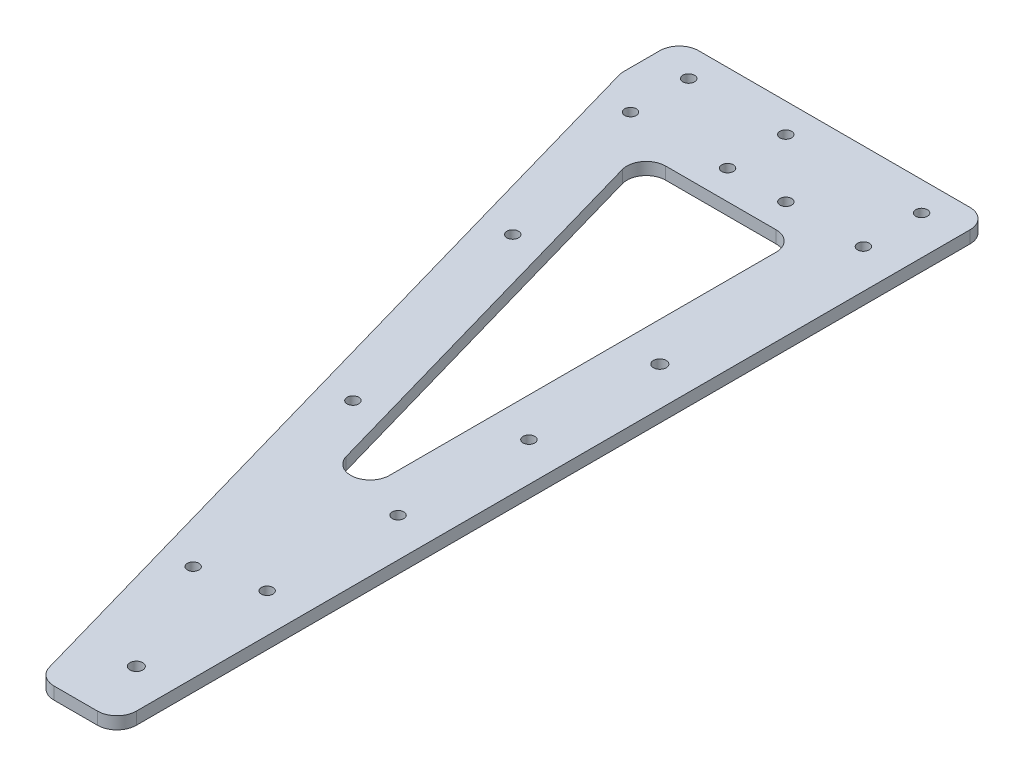
SolidWorks part; units mm, degrees
ref_plane "Front" through (0, 0, 0) normal (0, 0, 1) x (1, 0, 0)
ref_plane "Top" through (0, 0, 0) normal (0, 1, 0) x (1, 0, 0)
ref_plane "Right" through (0, 0, 0) normal (1, 0, 0) x (0, 0, -1)
sketch "Sketch1" plane through (0, 0, 0) normal (0, 1, 0) x (1, 0, 0)
  line L0 (-20, -210) -> (-80, 0)
  line L1 (0, 0) -> (-20, 0)
  line L2 (0, 0) -> (0, -210)
  line L3 (0, -210) -> (-20, -210)
  line L4 (-20, 0) -> (-20, -210)
  line L5 (-80, 0) -> (-20, 0)
  line L6 (-10, -210) -> (-10, -195)
  line L7 (-10, -195) -> (-10, -60)
  line L8 (-12.7886, -207.9396) -> (-70.057, -7.5)
  line L9 (-70.057, -7.5) -> (-20, -7.5)
  line L10 (-5.5771, -205.8792) -> (-60.1141, -15)
  line L11 (-60.1141, -15) -> (-20, -15)
  circle A0 centre (-10, -195) radius 1.65
  circle A1 centre (-10, -60) radius 1.65
  circle A2 centre (-70.057, -7.5) radius 1.5
  circle A3 centre (-45.0285, -7.5) radius 1.5
  circle A5 centre (-10, -127.5) radius 1500
  circle A6 centre (-10, -7.5) radius 1.5
  circle A7 centre (-10, -127.5) radius 1.5
  circle A8 centre (-10, -161.25) radius 1.5
  circle A9 centre (-10, -93.75) radius 1.5
  circle A10 centre (-41.4228, -107.7198) radius 1.5
  circle A11 centre (-57.9061, -50.0284) radius 1.5
  circle A12 centre (-24.9395, -165.4112) radius 1.5
  circle A13 centre (-30, -7.5) radius 1.5
  dimension "D6" = 7.5
  dimension "D7" = 33.75
  dimension "D10" = 60
  dimension "D1" = 20
  dimension "D2" = 210
  dimension "D3" = 60
  dimension "D4" = 15
  dimension "D5" = 135
  dimension "D8" = 33.75
  dimension "D11" = 60
  dimension "D12" = 10
  dimension "D9" = 15
extrude "Boss-Extrude1" add sketch "Sketch1" along normal blind 3.175 contours A13 L9 A3 A2 L8 A11 A10 A12 L4 L10 L11 | A13 L9 L4 L5 L0 L8 A12 A10 A11 A2 A3 | A9 A7 A8 L10 A0 L6 L3 L2 L1 L4 A1 A6 | A0 L7 L10 L4 L3 L6 | A0 L10 L7 region at (-15.8455, 0, 190.0164) region at (-47.9, 0, 104.4) region at (-9.434, 0, 96.6901) region at (-20.5128, 0, 174.2763) region at (-9.6978, 0, 192.425)
sketch "Sketch2" plane through (0, 0, 0) normal (0, -1, 0) x (1, 0, 0)
  line L0 (-80, 0) -> (0, 0)
  line L1 (-80, 0) -> (-80, -15)
  line L2 (0, 0) -> (0, -15)
  line L3 (-80, -15) -> (0, -15)
  line L4 (-70.057, 7.5) -> (-70.057, -7.5)
  line L5 (-45.0285, 7.5) -> (-45.0285, -7.5)
  line L6 (-10, 7.5) -> (-10, -7.5)
  circle A0 centre (-70.057, -7.5) radius 1.5
  circle A1 centre (-45.0285, -7.5) radius 1.5
  circle A2 centre (-10, -7.5) radius 1.5
  line M13 (-80, 0) -> (0, 0)
  dimension "D1" = 15
  dimension "D2" = 15
  dimension "D3" = 15
  dimension "D4" = 15
extrude "Boss-Extrude2" add sketch "Sketch2" against normal blind 3.175 contours A2 A1 L0 A0 L1 L3 L2 M13 region at (-39.9695, 0, -7.5)
fillet "Fillet1" radius 5 8 edges at (-20, 1.5875, 155.3992) (-20, 1.5875, 15) (-60.1141, 1.5875, 15) (-80, 1.5875, -15) (0, 1.5875, -15) (0, 1.5875, 210) (-20, 1.5875, 210) (-80, 1.5875, 0)
